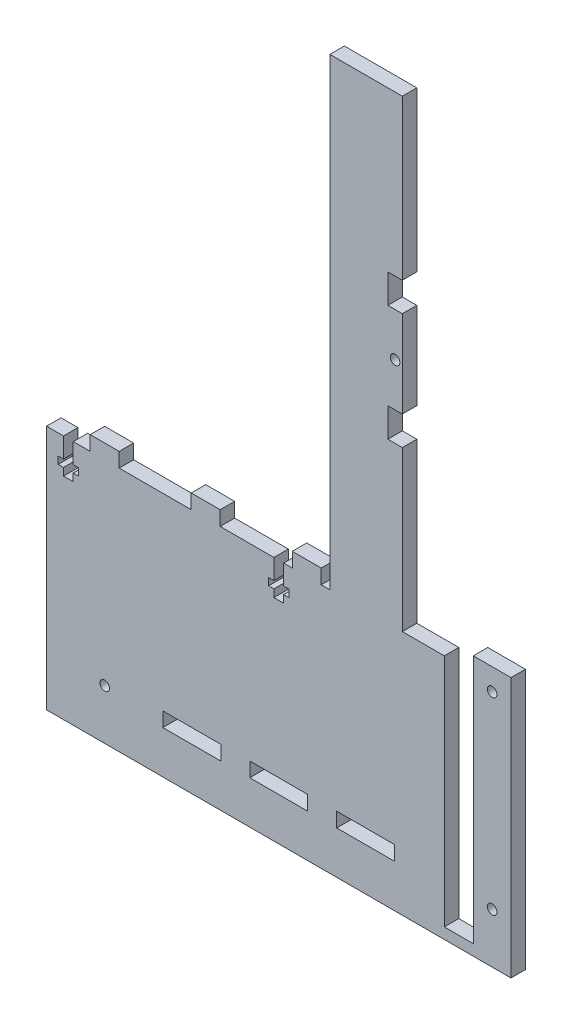
SolidWorks part; units mm, degrees
ref_plane "Front Plane" through (0, 0, 0) normal (0, 0, 1) x (1, 0, 0)
ref_plane "Top Plane" through (0, 0, 0) normal (0, 1, 0) x (1, 0, 0)
ref_plane "Right Plane" through (0, 0, 0) normal (1, 0, 0) x (0, 0, -1)
sketch "Sketch1" plane through (0, 0, 0) normal (0, 1, 0) x (1, 0, 0)
  line L0 (0, 15.4483) -> (0, 24.666) construction
  line L1 (-105.8938, 3.175) -> (97.6595, 3.175)
  line L2 (-105.8938, 3.175) -> (-105.8938, -3.175)
  line L3 (-105.8938, -3.175) -> (97.6595, -3.175)
  line L4 (97.6595, 3.175) -> (97.6595, -3.175)
  line L5 (8.1935, 0) -> (24.922, 0) construction
  line L6 (97.6595, -3.175) -> (97.6595, 3.175) construction
  arc A0 (-105.8105, 3.175) -> (104.0095, 224.9884) centre (110.0062, 9.1717) ccw construction
  dimension "D2" = 6.35
extrude "Base Extrusion" add sketch "Sketch1" along normal up to surface (107.6625 mm away)
sketch "Sketch4" plane through (0, 0, 3.175) normal (0, 0, 1) x (1, 0, 0)
  line L0 (97.6595, 25.1125) -> (-105.5405, 25.1125) construction
  line L1 (-54.9172, 25.1125) -> (-29.5172, 25.1125)
  line L2 (-54.9172, 25.1125) -> (-54.9172, 18.7625)
  line L3 (-54.9172, 18.7625) -> (-29.5172, 18.7625)
  line L4 (-29.5172, 25.1125) -> (-29.5172, 18.7625)
  line L5 (-16.8172, 25.1125) -> (8.5828, 25.1125)
  line L6 (-16.8172, 25.1125) -> (-16.8172, 18.7625)
  line L7 (-16.8172, 18.7625) -> (8.5828, 18.7625)
  line L8 (8.5828, 25.1125) -> (8.5828, 18.7625)
  line L9 (21.2828, 25.1125) -> (46.6828, 25.1125)
  line L10 (21.2828, 25.1125) -> (21.2828, 18.7625)
  line L11 (21.2828, 18.7625) -> (46.6828, 18.7625)
  line L12 (46.6828, 25.1125) -> (46.6828, 18.7625)
  line L13 (325.5529, 18.7625) -> (97.6595, 18.7625) construction
  line L14 (97.6595, 25.1125) -> (-105.5405, 25.1125) construction
  line L15 (325.5529, 18.7625) -> (97.6595, 18.7625) construction
  line L17 (-4.1172, 40.6411) -> (-4.1172, -10.2729) construction
  line L18 (-105.8938, 107.6625) -> (-105.8938, 0) construction
  line L19 (97.6595, 107.6625) -> (97.6595, 0) construction
  dimension "D1" = 25.4
  dimension "D2" = 25.4
  dimension "D3" = 25.4
  dimension "D5" = 12.7
  dimension "D6" = 12.7
extrude "Tab Holes to Chassis Base" cut sketch "Sketch4" against normal through all
sketch "Sketch5" plane through (0, 0, 3.175) normal (0, 0, 1) x (1, 0, 0)
  line L0 (-4.1172, 67.1576) -> (-4.1172, 113.4981) construction
  line L1 (-105.8938, 107.6625) -> (-105.8938, 0) construction
  line L2 (97.6595, 107.6625) -> (97.6595, 0) construction
  line L3 (97.6595, 107.6625) -> (-105.8938, 107.6625) construction
  line B0 (-1.9836, 107.6625) -> (-6.2508, 107.6625)
  line B1 (-6.2508, 95.7245) -> (-8.5622, 95.7245)
  line B2 (-8.5622, 95.7245) -> (-8.5622, 98.8995)
  line B3 (-8.5622, 98.8995) -> (-6.2508, 98.8995)
  line B4 (-6.2508, 98.8995) -> (-6.2508, 107.6625)
  line B5 (-6.2508, 95.7245) -> (-6.2508, 92.4225)
  line B6 (-6.2508, 92.4225) -> (-1.9836, 92.4225)
  line B7 (-1.9836, 95.7245) -> (-1.9836, 92.4225)
  line B8 (-1.9836, 98.8995) -> (-1.9836, 107.6625)
  line B9 (0.3278, 98.8995) -> (-1.9836, 98.8995)
  line B10 (0.3278, 95.7245) -> (0.3278, 98.8995)
  line B11 (-1.9836, 95.7245) -> (0.3278, 95.7245)
sketch_block_instance "TSlot-1"
sketch_block "TSlot" parameters "D1"=3.302, "D2"=3.175
extrude "T Slot Center" cut sketch "Sketch5" against normal through all
sketch "Sketch6" plane through (0, 0, 3.175) normal (0, 0, 1) x (1, 0, 0)
  line L0 (97.6595, 107.6625) -> (-1.9836, 107.6625) construction
  line L1 (50.0345, 107.6625) -> (18.2845, 107.6625)
  line L2 (50.0345, 107.6625) -> (50.0345, 310.8625)
  line L3 (50.0345, 310.8625) -> (18.2845, 310.8625)
  line L4 (18.2845, 107.6625) -> (18.2845, 310.8625)
  line L5 (50.0345, 25.1125) -> (50.0345, 177.5125) construction
  line L6 (43.6845, 310.8625) -> (50.0345, 310.8625) construction
  dimension "D1" = 31.75
extrude "Arm Support" add sketch "Sketch6" against normal up to surface (6.35 mm away) up to face at (-4.1172, 87.1244, -3.175)
sketch "Sketch8" plane through (0, 107.6625, 0) normal (0, 1, 0) x (1, 0, 0)
  line L0 (68.4283, -3.175) -> (68.4283, 3.175)
  line L1 (68.4283, -3.175) -> (81.1283, -3.175)
  line L2 (68.4283, 3.175) -> (81.1283, 3.175)
  line L3 (81.1283, -3.175) -> (81.1283, 3.175)
  line L4 (97.6595, -3.175) -> (50.0345, -3.175) construction
  line L5 (50.0345, 3.175) -> (97.6595, 3.175) construction
  line L6 (74.7783, -7.9885) -> (74.7783, 24.6597) construction
  line L7 (81.1283, 3.175) -> (81.1283, 85.725) construction
  line L8 (68.4283, 85.725) -> (68.4283, 3.175) construction
extrude "Arm Clearance" cut sketch "Sketch8" against normal offset from surface (102.9 mm away) 4.7625 up to face at (-4.1172, 0, 0)
sketch "Sketch9" plane through (0, 0, 3.175) normal (0, 0, 1) x (1, 0, 0)
  line L0 (96.3524, 21.9375) -> (106.7258, 21.9375) construction
  line L1 (104.0095, 25.1125) -> (97.6595, 25.1125) construction
  line L2 (104.0095, 18.7625) -> (97.6595, 18.7625) construction
  line L3 (89.3939, 25.5557) -> (89.3939, 3.267) construction
  line L4 (81.1283, 4.7625) -> (81.1283, 107.6625) construction
  line L5 (97.6595, 107.6625) -> (97.6595, 0) construction
  circle A0 centre (89.3939, 21.9375) radius 2.0955
  dimension "D1" = 4.191
extrude "Base Mounting Hole 1" cut sketch "Sketch9" against normal through all
sketch "Sketch10" plane through (0, 0, 3.175) normal (0, 0, 1) x (1, 0, 0)
  line L0 (-78.6997, 21.9375) -> (-124.1873, 21.9375) construction
  line L5 (-29.5172, 25.1125) -> (-54.9172, 25.1125) construction
  line L6 (-54.9172, 18.7625) -> (-29.5172, 18.7625) construction
  line L7 (-80.4055, 38.7875) -> (-80.4055, -6.1881) construction
  line L8 (-105.8938, 107.6625) -> (-105.8938, 0) construction
  line L9 (-54.9172, 25.1125) -> (-54.9172, 18.7625) construction
  circle A0 centre (-80.4055, 21.9375) radius 2.0955
  circle A1 centre (89.3939, 21.9375) radius 2.0955 construction
extrude "Base Mounting Hole 2" cut sketch "Sketch10" against normal through all
sketch "Sketch11" plane through (0, 0, 3.175) normal (0, 0, 1) x (1, 0, 0)
  line L0 (39.2564, 209.2625) -> (78.7704, 209.2625) construction
  line L1 (50.0345, 211.3961) -> (43.6845, 211.3961) construction
  line L2 (43.6845, 207.1289) -> (50.0345, 207.1289) construction
  line L3 (46.8595, 189.1979) -> (46.8595, 134.4872) construction
  line L4 (50.0345, 310.8625) -> (50.0345, 107.6625) construction
  line L5 (43.6845, 211.3961) -> (43.6845, 228.3125) construction
  circle A0 centre (46.8595, 209.2625) radius 2.0955
  circle A1 centre (89.3939, 21.9375) radius 2.0955 construction
extrude "Arm Support Mounting Hole" cut sketch "Sketch11" against normal through all
sketch "Sketch12" plane through (0, 0, 3.175) normal (0, 0, 1) x (1, 0, 0)
  line L0 (50.0345, 107.6625) -> (50.0345, 310.8625) construction
  line L1 (43.6845, 241.0125) -> (50.0345, 241.0125)
  line L2 (43.6845, 241.0125) -> (43.6845, 228.3125)
  line L3 (43.6845, 228.3125) -> (50.0345, 228.3125)
  line L4 (50.0345, 241.0125) -> (50.0345, 228.3125)
  line L5 (43.6845, 190.2125) -> (50.0345, 190.2125)
  line L6 (43.6845, 190.2125) -> (43.6845, 177.5125)
  line L7 (43.6845, 177.5125) -> (50.0345, 177.5125)
  line L8 (50.0345, 190.2125) -> (50.0345, 177.5125)
  line L9 (43.6845, 177.5125) -> (43.6845, 190.2125) construction
  line L10 (43.6845, 190.2125) -> (50.0345, 190.2125) construction
  line L11 (50.0345, 177.5125) -> (43.6845, 177.5125) construction
  line L12 (43.6845, 228.3125) -> (43.6845, 241.0125) construction
  line L13 (43.6845, 241.0125) -> (50.0345, 241.0125) construction
  line L14 (50.0345, 228.3125) -> (43.6845, 228.3125) construction
extrude "Arm Support Tab Slots" cut sketch "Sketch12" against normal through all
sketch "Sketch13" plane through (0, 107.6625, 0) normal (0, 1, 0) x (1, 0, 0)
  line L0 (-105.8938, 3.175) -> (-6.2508, 3.175) construction
  line L1 (81.1283, 3.175) -> (97.6595, 3.175)
  line L2 (81.1283, 3.175) -> (81.1283, -3.175)
  line L3 (81.1283, -3.175) -> (97.6595, -3.175)
  line L4 (97.6595, 3.175) -> (97.6595, -3.175)
  line L5 (-86.7555, 3.175) -> (-74.0555, 3.175)
  line L6 (-86.7555, 3.175) -> (-86.7555, -3.175)
  line L7 (-86.7555, -3.175) -> (-74.0555, -3.175)
  line L8 (-74.0555, 3.175) -> (-74.0555, -3.175)
  line L9 (-6.2508, -3.175) -> (-105.8938, -3.175) construction
  line L10 (-1.9836, 3.175) -> (18.2845, 3.175) construction
  line L11 (1.8005, 3.175) -> (14.5005, 3.175)
  line L12 (1.8005, 3.175) -> (1.8005, -3.175)
  line L13 (1.8005, -3.175) -> (14.5005, -3.175)
  line L14 (14.5005, 3.175) -> (14.5005, -3.175)
  line L15 (18.2845, -3.175) -> (-1.9836, -3.175) construction
  line L16 (8.1505, 19.4293) -> (8.1505, -15.2554) construction
  line L17 (-42.4775, 3.175) -> (-29.7775, 3.175)
  line L18 (-42.4775, 3.175) -> (-42.4775, -3.175)
  line L19 (-42.4775, -3.175) -> (-29.7775, -3.175)
  line L20 (-29.7775, 3.175) -> (-29.7775, -3.175)
  line L21 (18.2845, 3.175) -> (18.2845, -3.175) construction
  line L22 (-1.9836, 3.175) -> (-1.9836, -3.175) construction
  line L23 (-80.4055, 22.3632) -> (-80.4055, -15.2554) construction
  line L26 (-82.5391, 11.938) -> (-82.5391, 3.175) construction
  line L27 (-78.2719, 3.175) -> (-78.2719, 11.938) construction
  line L28 (-36.1275, 22.3632) -> (-36.1275, -21.1411) construction
  dimension "D1" = 12.7
extrude "Top Plate Tab" add sketch "Sketch13" along normal blind 6.35
sketch "Sketch14" plane through (0, 0, 3.175) normal (0, 0, 1) x (1, 0, 0)
  line L0 (-96.3247, 71.8951) -> (-96.3247, 106.4008) construction
  line L1 (-86.7555, 107.6625) -> (-105.8938, 107.6625) construction
  line L2 (-105.8938, 107.6625) -> (-105.8938, 0) construction
  line L3 (-86.7555, 114.0125) -> (-86.7555, 107.6625) construction
  line B0 (-94.1911, 107.6625) -> (-98.4583, 107.6625)
  line B1 (-98.4583, 95.7245) -> (-100.7697, 95.7245)
  line B2 (-100.7697, 95.7245) -> (-100.7697, 98.8995)
  line B3 (-100.7697, 98.8995) -> (-98.4583, 98.8995)
  line B4 (-98.4583, 98.8995) -> (-98.4583, 107.6625)
  line B5 (-98.4583, 95.7245) -> (-98.4583, 92.4225)
  line B6 (-98.4583, 92.4225) -> (-94.1911, 92.4225)
  line B7 (-94.1911, 95.7245) -> (-94.1911, 92.4225)
  line B8 (-94.1911, 98.8995) -> (-94.1911, 107.6625)
  line B9 (-91.8797, 98.8995) -> (-94.1911, 98.8995)
  line B10 (-91.8797, 95.7245) -> (-91.8797, 98.8995)
  line B11 (-94.1911, 95.7245) -> (-91.8797, 95.7245)
sketch_block_instance "TSlot-3"
extrude "T Slot Top Corner" cut sketch "Sketch14" against normal through all
sketch "Sketch15" plane through (0, 0, 3.175) normal (0, 0, 1) x (1, 0, 0)
  line L0 (89.3939, 99.797) -> (89.3939, 89.693) construction
  line L1 (81.1283, 4.7625) -> (81.1283, 114.0125) construction
  line L2 (97.6595, 114.0125) -> (97.6595, 0) construction
  line L3 (95.644, 104.4907) -> (106.8624, 104.4907) construction
  line L7 (62.3812, 94.9689) -> (80.775, 94.9689) construction
  line L8 (1.8005, 114.0125) -> (14.5005, 114.0125) construction
  circle A0 centre (89.3939, 104.4907) radius 2.0955
  dimension "D1" = 4.191
extrude "Cut-Extrude8" cut sketch "Sketch15" against normal through all
